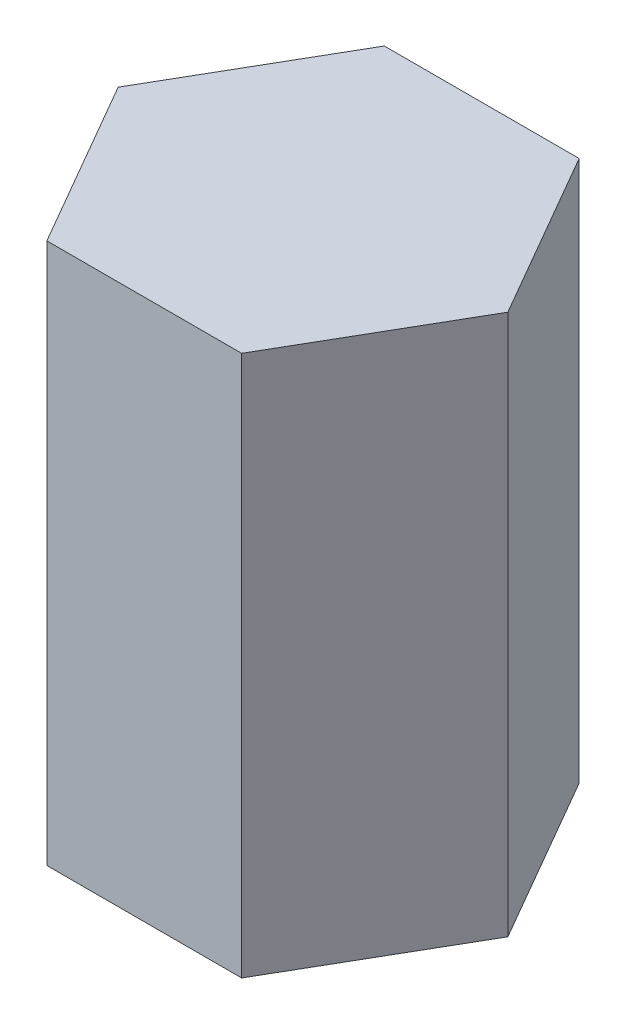
SolidWorks part; units mm, degrees
other "Markup1"
sketch "Sketch4" plane through (577.3503, 1603, 500) normal (0.5856, 0.3664, 0.723) x (0.7705, 0.0254, -0.6369)
material "Bus"
ref_plane "Front Plane" through (0, 0, 0) normal (0, 0, 1) x (1, 0, 0)
ref_plane "Top Plane" through (0, 0, 0) normal (0, 1, 0) x (1, 0, 0)
ref_plane "Right Plane" through (0, 0, 0) normal (1, 0, 0) x (0, 0, -1)
sketch "Sketch2" plane through (0, 0, 0) normal (0, 1, 0) x (1, 0, 0)
  line L1 (577.3503, 0) -> (288.6751, 500)
  line L2 (288.6751, 500) -> (-288.6751, 500)
  line L3 (-288.6751, 500) -> (-577.3503, 0)
  line L4 (-577.3503, 0) -> (-288.6751, -500)
  line L5 (-288.6751, -500) -> (288.6751, -500)
  line L6 (288.6751, -500) -> (577.3503, 0)
  circle A0 centre (0, 0) radius 500 construction
  dimension "D1" = 1000
extrude "Boss-Extrude1" add sketch "Sketch2" along normal blind 1603
ref_axis "Axis1" through (0, -313.0569, 0) along (0, 1, 0)
ref_plane "Plane2" through (0, 400.75, 0) normal (0, 1, 0) x (1, 0, 0)
sketch "Sketch3" plane through (0, 400.75, 0) normal (0, 1, 0) x (1, 0, 0)
  line L0 (288.6751, 500) -> (-288.6751, 500) construction
  line L1 (575.0409, 0) -> (287.5204, 498)
  line L2 (287.5204, 498) -> (-287.5204, 498)
  line L3 (-287.5204, 498) -> (-575.0409, 0)
  line L4 (-575.0409, 0) -> (-287.5204, -498)
  line L5 (-287.5204, -498) -> (287.5204, -498)
  line L6 (287.5204, -498) -> (575.0409, 0)
  circle A0 centre (0, 0) radius 498 construction
  dimension "D1" = 996
extrude "Cut-Extrude1" cut sketch "Sketch3" along normal blind 1200.3
